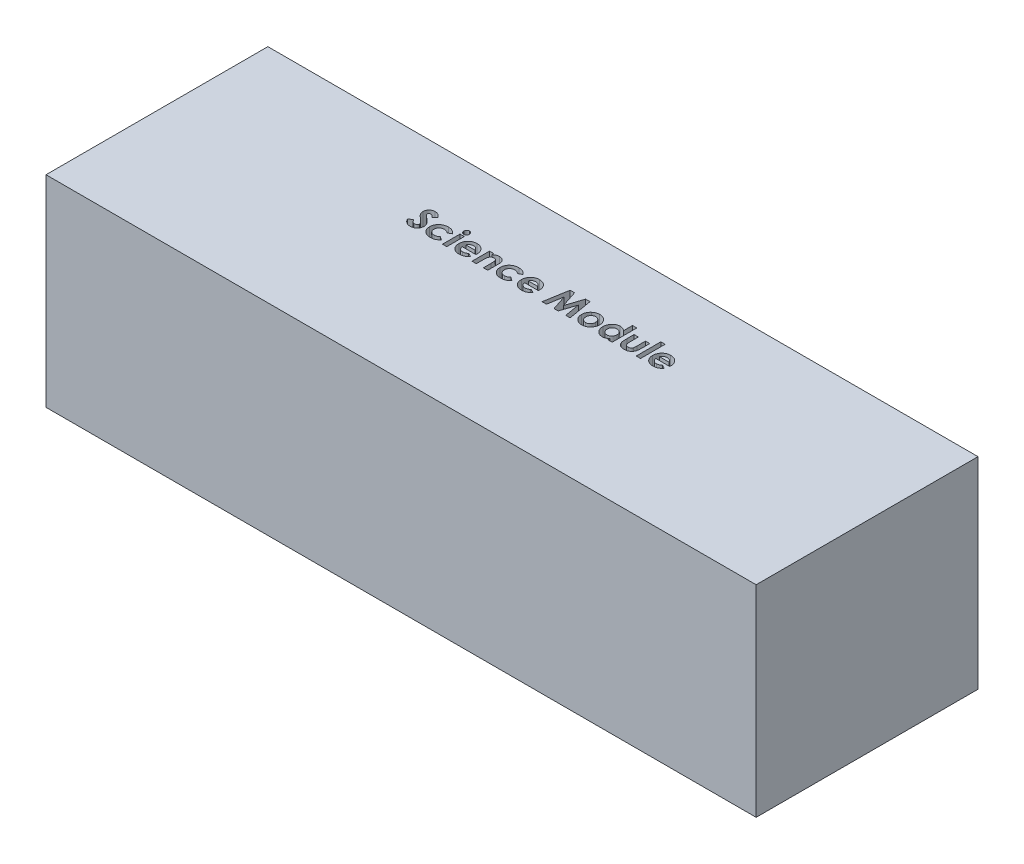
SolidWorks part; units mm, degrees
ref_plane "Front Plane" through (0, 0, 0) normal (0, 0, 1) x (1, 0, 0)
ref_plane "Top Plane" through (0, 0, 0) normal (0, 1, 0) x (1, 0, 0)
ref_plane "Right Plane" through (0, 0, 0) normal (1, 0, 0) x (0, 0, -1)
sketch "Sketch1" plane through (0, 0, 0) normal (0, 1, 0) x (1, 0, 0)
  line L1 (0, 0) -> (564, 0)
  line L2 (0, 0) -> (0, 176.2014)
  line L3 (0, 176.2014) -> (564, 176.2014)
  line L4 (564, 0) -> (564, 176.2014)
  dimension "D1" = 564
  dimension "D2" = 176.2014
extrude "Boss-Extrude1" add sketch "Sketch1" along normal blind 160 contours L1 L4 L3 L2 region at (282, 0, -88.1007)
sketch "Sketch2" plane through (0, 160, 0) normal (0, 1, 0) x (1, 0, 0)
  line L0 (173.2077, 109.6768) -> (457.0401, 109.6768) construction
  text T0 "<b>Science Module</b>" font "Century Gothic" height in points 72
extrude "Cut-Extrude1" cut sketch "Sketch2" against normal blind 160
